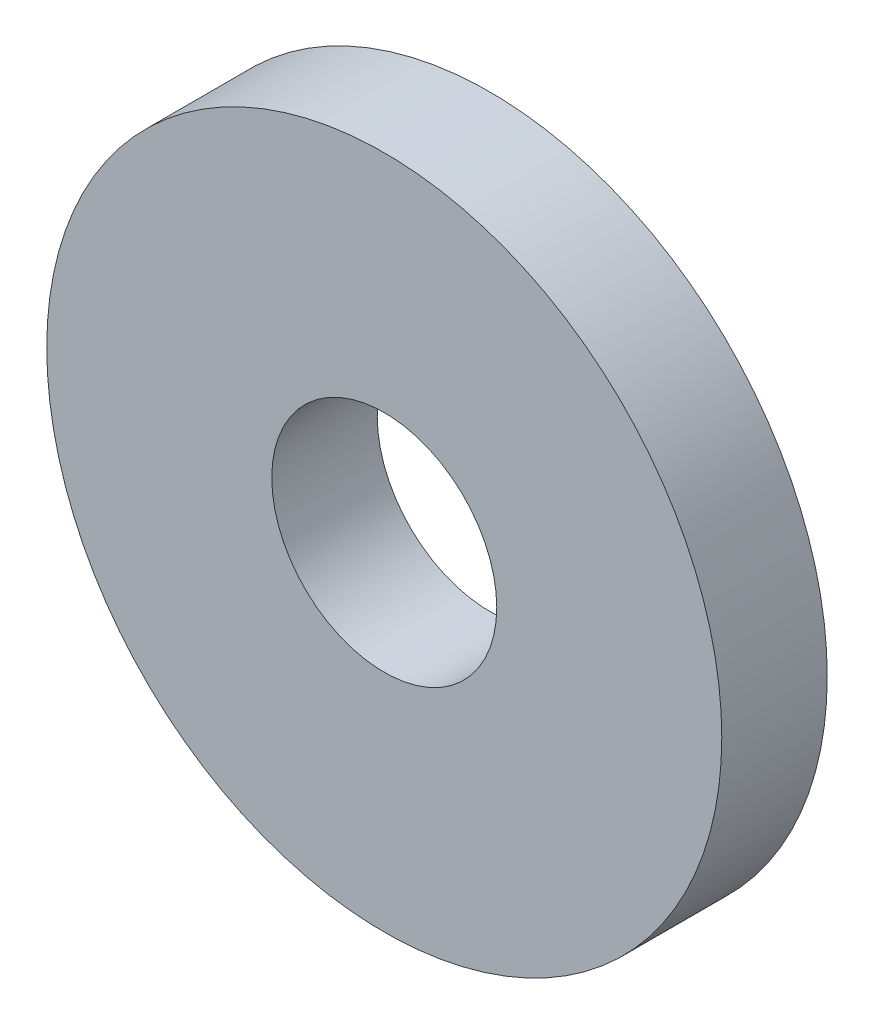
SolidWorks part; units mm, degrees
ref_plane "Front Plane" through (0, 0, 0) normal (0, 0, 1) x (1, 0, 0)
ref_plane "Top Plane" through (0, 0, 0) normal (0, 1, 0) x (1, 0, 0)
ref_plane "Right Plane" through (0, 0, 0) normal (1, 0, 0) x (0, 0, -1)
sketch "Sketch1" plane through (0, 0, 0) normal (0, 0, 1) x (1, 0, 0)
  circle A0 centre (0, 0) radius 12.7
  circle A1 centre (0, 0) radius 4.2333
  dimension "D1" = 8.4667
  dimension "D2" = 25.4
extrude "Boss-Extrude1" add sketch "Sketch1" along normal blind 3.9688
scale "Scale1" scale about centroid uniform scaling yes scale factor 0.75
